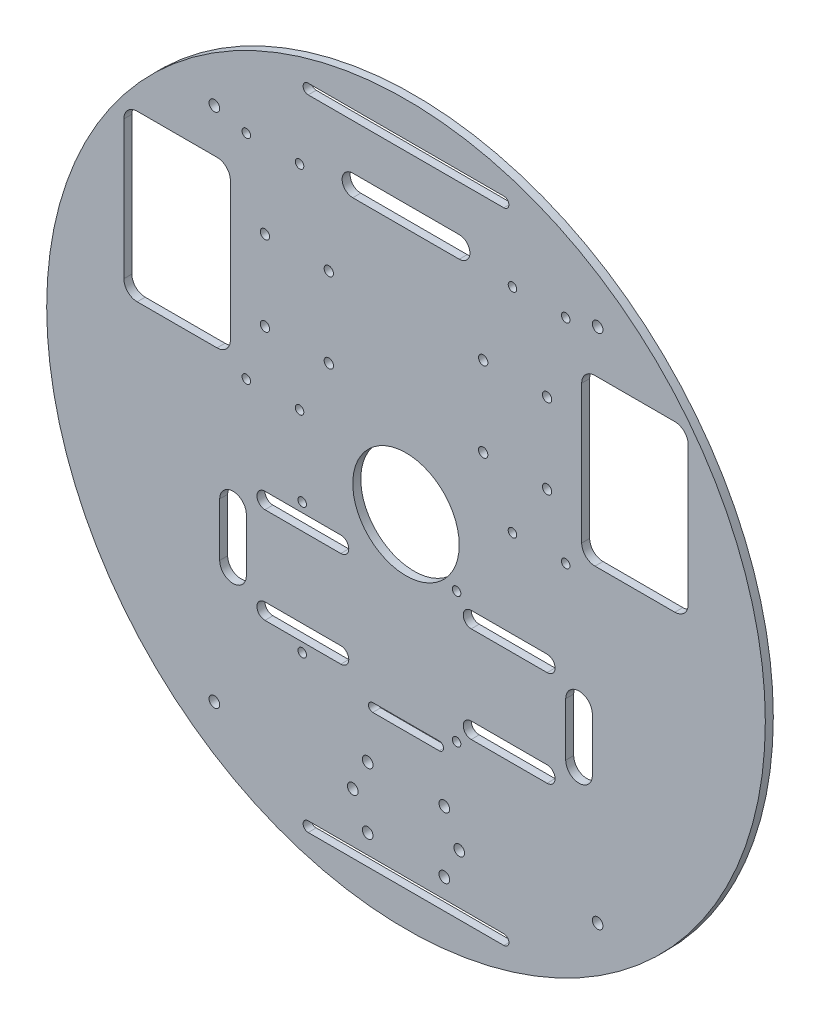
SolidWorks part; units mm, degrees
ref_plane "前视基准面" through (0, 0, 0) normal (0, 0, 1) x (1, 0, 0)
ref_plane "上视基准面" through (0, 0, 0) normal (0, 1, 0) x (1, 0, 0)
ref_plane "右视基准面" through (0, 0, 0) normal (1, 0, 0) x (0, 0, -1)
sketch "草图1" plane through (0, 0, 0) normal (0, 0, 1) x (1, 0, 0)
  line L0 (0, 135) -> (0, -135) construction
  line L1 (0, -99.3042) -> (86, 49.6521) construction
  line L2 (86, 49.6521) -> (-86, 49.6521) construction
  line L3 (-86, 49.6521) -> (0, -99.3042) construction
  line L4 (-106, 80.6521) -> (-66, 80.6521)
  line L5 (-106, 80.6521) -> (-106, 18.6521)
  line L6 (-106, 18.6521) -> (-66, 18.6521)
  line L7 (-66, 80.6521) -> (-66, 18.6521)
  line L8 (-106, 80.6521) -> (-66, 18.6521) construction
  line L9 (-106, 18.6521) -> (-66, 80.6521) construction
  line L10 (106, 80.6521) -> (66, 80.6521)
  line L11 (66, 80.6521) -> (66, 18.6521)
  line L12 (106, 80.6521) -> (66, 18.6521) construction
  line L13 (106, 18.6521) -> (66, 18.6521)
  line L14 (106, 18.6521) -> (66, 80.6521) construction
  line L15 (106, 80.6521) -> (106, 18.6521)
  line L17 (-14.4, -87.8042) -> (14.4, -87.8042) construction
  line L18 (-14.4, -87.8042) -> (-14.4, -110.8042) construction
  line L19 (-14.4, -110.8042) -> (14.4, -110.8042) construction
  line L20 (14.4, -87.8042) -> (14.4, -110.8042) construction
  line L21 (-14.4, -87.8042) -> (14.4, -110.8042) construction
  line L22 (-14.4, -110.8042) -> (14.4, -87.8042) construction
  line L29 (-53, 64.6521) -> (-29, 64.6521) construction
  line L30 (-53, 64.6521) -> (-53, 34.6521) construction
  line L31 (-53, 34.6521) -> (-29, 34.6521) construction
  line L32 (-29, 64.6521) -> (-29, 34.6521) construction
  line L33 (-53, 64.6521) -> (-29, 34.6521) construction
  line L34 (-53, 34.6521) -> (-29, 64.6521) construction
  circle A0 centre (0, 0) radius 135
  circle A1 centre (0, 0) radius 49.6521 construction
  circle A2 centre (-53, 64.6521) radius 1.75
  circle A3 centre (-29, 64.6521) radius 1.75
  circle A4 centre (-53, 34.6521) radius 1.75
  circle A5 centre (-29, 34.6521) radius 1.75
  circle A6 centre (53, 34.6521) radius 1.75
  circle A7 centre (29, 34.6521) radius 1.75
  circle A8 centre (29, 64.6521) radius 1.75
  circle A9 centre (53, 64.6521) radius 1.75
  circle A10 centre (20, -99.3042) radius 2
  circle A11 centre (14.4, -87.8042) radius 2
  circle A12 centre (14.4, -110.8042) radius 2
  circle A13 centre (-14.4, -87.8042) radius 2
  circle A14 centre (-14.4, -110.8042) radius 2
  circle A15 centre (-20, -99.3042) radius 2
  point P25 (0, 49.6521)
  point P26 (-41, 49.6521)
  point P30 (0, 49.6521)
  dimension "D1" = 270
  dimension "D9" = 3.5
  dimension "D10" = 3.5
  dimension "D11" = 3.5
  dimension "D12" = 3.5
  dimension "D14" = 20
  dimension "D2" = 40
  dimension "D3" = 62
  dimension "D4" = 41
  dimension "D5" = 25
  dimension "D6" = 28.8
  dimension "D7" = 24
  dimension "D8" = 30
  dimension "D13" = 23
extrude "凸台-拉伸1" add sketch "草图1" along normal blind 3 contours A0 A14 A9 A7 L10 L15 L13 L11 A2 A3 A4 A5 A6 A8 A10 A11 A12 A13 A15 region at (0, -4.6527, 0)
fillet "圆角1" radius 5 8 edges at (106, 80.6521, 1.5) (66, 80.6521, 1.5) (66, 18.6521, 1.5) (106, 18.6521, 1.5) (-66, 18.6521, 1.5) (-106, 18.6521, 1.5) (-106, 80.6521, 1.5) (-66, 80.6521, 1.5)
sketch "草图2" plane through (0, 0, 3) normal (0, 0, 1) x (1, 0, 0)
  line L1 (-72, 97) -> (72, 97) construction
  line L2 (-72, 97) -> (-72, -97) construction
  line L3 (-72, -97) -> (72, -97) construction
  line L4 (72, 97) -> (72, -97) construction
  line L5 (-72, 97) -> (72, -97) construction
  line L6 (-72, -97) -> (72, 97) construction
  line L7 (24.5056, -55) -> (53, -55)
  line L8 (-53, -19) -> (-24.5056, -19)
  line L9 (-53, -19) -> (-53, -61) construction
  line L10 (-53, -61) -> (-24.5056, -61)
  line L11 (53, -19) -> (53, -61) construction
  line L12 (-53, -19) -> (53, -61) construction
  line L13 (-53, -61) -> (53, -19) construction
  line L14 (-53, -25) -> (-24.5056, -25)
  line L15 (-53, -25) -> (-53, -55) construction
  line L16 (-53, -55) -> (-24.5056, -55)
  line L17 (53, -25) -> (53, -55) construction
  line L18 (-53, -25) -> (53, -55) construction
  line L19 (-53, -55) -> (53, -25) construction
  line L20 (24.5056, -25) -> (53, -25)
  line L21 (24.5056, -19) -> (53, -19)
  line L22 (24.5056, -61) -> (53, -61)
  line L23 (40, 94) -> (40, 14) construction
  line L24 (-65, -30) -> (65, -30) construction
  line L25 (-65, -30) -> (-65, -50) construction
  line L26 (-65, -50) -> (65, -50) construction
  line L27 (65, -30) -> (65, -50) construction
  line L28 (-65, -30) -> (65, -50) construction
  line L29 (-65, -50) -> (65, -30) construction
  line L30 (-70, -30) -> (-60, -30) construction
  line L31 (-70, -30) -> (-70, -50)
  line L32 (-70, -50) -> (-60, -50) construction
  line L33 (-60, -30) -> (-60, -50)
  line L34 (-70, -30) -> (-60, -50) construction
  line L35 (-70, -50) -> (-60, -30) construction
  line L36 (60, -30) -> (70, -30) construction
  line L37 (60, -30) -> (60, -50)
  line L38 (60, -50) -> (70, -50) construction
  line L39 (70, -30) -> (70, -50)
  line L40 (60, -30) -> (70, -50) construction
  line L41 (60, -50) -> (70, -30) construction
  line L43 (35, -12.5) -> (-35, -12.5) construction
  line L44 (35, -12.5) -> (35, -67.5) construction
  line L45 (-42.5, -12) -> (42.5, -12) construction
  line L46 (-42.5, -12) -> (-42.5, -68) construction
  line L47 (-42.5, -68) -> (42.5, -68) construction
  line L48 (-135, 0) -> (135, 0) construction
  line L49 (-36.7556, -118.1) -> (36.7556, -121.9) construction
  line L50 (-36.7556, 121.9) -> (36.7556, 121.9)
  line L51 (-36.7556, 121.9) -> (-36.7556, 118.1) construction
  line L52 (-36.7556, 118.1) -> (36.7556, 118.1)
  line L53 (36.7556, 121.9) -> (36.7556, 118.1) construction
  line L54 (-36.7556, 121.9) -> (36.7556, 118.1) construction
  line L55 (-36.7556, 118.1) -> (36.7556, 121.9) construction
  line L56 (-36.7556, -121.9) -> (36.7556, -118.1) construction
  line L57 (36.7556, -121.9) -> (36.7556, -118.1) construction
  line L58 (-36.7556, -121.9) -> (-36.7556, -118.1) construction
  line L59 (-36.7556, -118.1) -> (36.7556, -118.1)
  line L60 (-36.7556, -121.9) -> (36.7556, -121.9)
  line L61 (-40, 94) -> (-40, 14) construction
  line L62 (-60, 94) -> (60, 94) construction
  line L63 (-60, 94) -> (-60, 14) construction
  line L64 (-60, 14) -> (60, 14) construction
  line L65 (60, 94) -> (60, 14) construction
  line L66 (-60, 94) -> (60, 14) construction
  line L67 (-60, 14) -> (60, 94) construction
  line L68 (42.5, -12) -> (42.5, -68) construction
  line L69 (-42.5, -12) -> (42.5, -68) construction
  line L70 (-42.5, -68) -> (42.5, -12) construction
  line L71 (-39, -15.5) -> (19, -15.5) construction
  line L72 (-39, -15.5) -> (-39, -64.5) construction
  line L73 (-39, -64.5) -> (19, -64.5) construction
  line L74 (19, -15.5) -> (19, -64.5) construction
  line L75 (-39, -15.5) -> (19, -64.5) construction
  line L76 (-39, -64.5) -> (19, -15.5) construction
  line L77 (35, -67.5) -> (-35, -67.5) construction
  line L78 (-35, -12.5) -> (-35, -67.5) construction
  line L79 (35, -12.5) -> (-35, -67.5) construction
  line L80 (35, -67.5) -> (-35, -12.5) construction
  line L81 (12.5, -70.7) -> (-12.5, -70.7)
  line L82 (12.5, -70.7) -> (12.5, -67.5) construction
  line L83 (12.5, -67.5) -> (-12.5, -67.5)
  line L84 (-12.5, -70.7) -> (-12.5, -67.5) construction
  line L85 (12.5, -70.7) -> (-12.5, -67.5) construction
  line L86 (12.5, -67.5) -> (-12.5, -70.7) construction
  line L87 (20, 101) -> (-20, 101)
  line L88 (20, 101) -> (20, 93) construction
  line L89 (20, 93) -> (-20, 93)
  line L90 (-20, 101) -> (-20, 93) construction
  line L91 (20, 101) -> (-20, 93) construction
  line L92 (20, 93) -> (-20, 101) construction
  circle A0 centre (0, 0) radius 20
  circle A1 centre (-72, 97) radius 2
  circle A2 centre (72, 97) radius 2
  circle A3 centre (72, -97) radius 2
  circle A4 centre (-72, -97) radius 2
  arc A5 (-53, -19) -> (-53, -25) centre (-53, -22) ccw
  arc A6 (-53, -55) -> (-53, -61) centre (-53, -58) ccw
  arc A7 (-24.5056, -19) -> (-24.5056, -25) centre (-24.5056, -22) cw
  arc A8 (-24.5056, -61) -> (-24.5056, -55) centre (-24.5056, -58) ccw
  arc A9 (53, -55) -> (53, -61) centre (53, -58) cw
  arc A10 (53, -19) -> (53, -25) centre (53, -22) cw
  arc A11 (24.5056, -61) -> (24.5056, -55) centre (24.5056, -58) cw
  arc A12 (24.5056, -19) -> (24.5056, -25) centre (24.5056, -22) ccw
  arc A13 (-70, -30) -> (-60, -30) centre (-65, -30) cw
  arc A14 (-70, -50) -> (-60, -50) centre (-65, -50) ccw
  arc A15 (60, -30) -> (70, -30) centre (65, -30) cw
  arc A16 (60, -50) -> (70, -50) centre (65, -50) ccw
  circle A17 centre (-60, 94) radius 1.6
  circle A18 centre (-60, 14) radius 1.6
  circle A19 centre (-40, 94) radius 1.6
  circle A20 centre (-40, 14) radius 1.6
  circle A21 centre (60, 14) radius 1.6
  circle A22 centre (60, 94) radius 1.6
  circle A23 centre (40, 94) radius 1.6
  circle A24 centre (40, 14) radius 1.6
  circle A25 centre (0, 0) radius 135 construction
  arc A26 (36.7556, 121.9) -> (36.7556, 118.1) centre (36.7556, 120) cw
  arc A27 (-36.7556, 121.9) -> (-36.7556, 118.1) centre (-36.7556, 120) ccw
  arc A28 (-36.7556, -121.9) -> (-36.7556, -118.1) centre (-36.7556, -120) cw
  arc A29 (36.7556, -121.9) -> (36.7556, -118.1) centre (36.7556, -120) ccw
  circle A30 centre (-39, -15.5) radius 1.6
  circle A31 centre (19, -15.5) radius 1.6
  circle A32 centre (-39, -64.5) radius 1.6
  circle A33 centre (19, -64.5) radius 1.6
  arc A34 (-12.5, -67.5) -> (-12.5, -70.7) centre (-12.5, -69.1) ccw
  arc A35 (12.5, -67.5) -> (12.5, -70.7) centre (12.5, -69.1) cw
  arc A36 (20, 101) -> (20, 93) centre (20, 97) cw
  arc A37 (-20, 101) -> (-20, 93) centre (-20, 97) ccw
  point P25 (0, 54)
  point P32 (0, -40)
  point P37 (-65, -40)
  point P38 (0, -40)
  point P39 (0, -40)
  point P52 (65, -40)
  point P61 (0, -40)
  point P77 (-10, -40)
  point P83 (0, 120)
  point P96 (0, -120)
  point P97 (0, -40)
  point P106 (-42.5, -40)
  point P111 (0, -40)
  point P116 (0, -69.1)
  dimension "D1" = 144
  dimension "D13" = 3.8
  dimension "D15" = 4
  dimension "D16" = 4
  dimension "D17" = 4
  dimension "D18" = 4
  dimension "D12" = 56
  dimension "D26" = 6
  dimension "D27" = 3
  dimension "D28" = 3
  dimension "D2" = 194
  dimension "D3" = 30
  dimension "D4" = 20
  dimension "D5" = 106
  dimension "D6" = 130
  dimension "D7" = 40
  dimension "D8" = 10
  dimension "D9" = 10
  dimension "D10" = 54
  dimension "D14" = 120
  dimension "D19" = 80
  dimension "D20" = 120
  dimension "D21" = 85
  dimension "D22" = 3.5
  dimension "D23" = 58
  dimension "D24" = 49
  dimension "D25" = 3.5
  dimension "D29" = 70
  dimension "D30" = 55
  dimension "D31" = 25
  dimension "D32" = 3.2
  dimension "D33" = 8
  dimension "D34" = 40
extrude "切除-拉伸1" cut sketch "草图2" against normal blind 10
sketch "草图3" plane through (0, 0, 3) normal (0, 0, 1) x (1, 0, 0)
  line L0 (0, 0) -> (0, -135) construction
  line L1 (0, 93) -> (0, 0) construction
  line L2 (35, -8.8786) -> (-35, -8.8786) construction
  line L3 (35, -8.8786) -> (35, -63.8786) construction
  line L4 (35, -63.8786) -> (-35, -63.8786) construction
  line L5 (-35, -8.8786) -> (-35, -63.8786) construction
  line L6 (35, -8.8786) -> (-35, -63.8786) construction
  line L7 (35, -63.8786) -> (-35, -8.8786) construction
  line L8 (-20, 93) -> (20, 93) construction
  circle A0 centre (0, 0) radius 135 construction
  point P6 (0, -36.3786)
  dimension "D1" = 55
  dimension "D2" = 70
  dimension "D3" = 93
sketch "草图4" plane through (0, 0, 0) normal (0, 0, -1) x (-1, 0, 0)
  line L1 (-88.3346, 51) -> (0, -102)
  line L2 (0, -102) -> (88.3346, 51)
  line L3 (88.3346, 51) -> (-88.3346, 51)
  circle A0 centre (0, 0) radius 102 construction
  point P1 (0, 51)
  dimension "D3" = 204
  dimension "D1" = 176.6692
  dimension "D2" = 153
